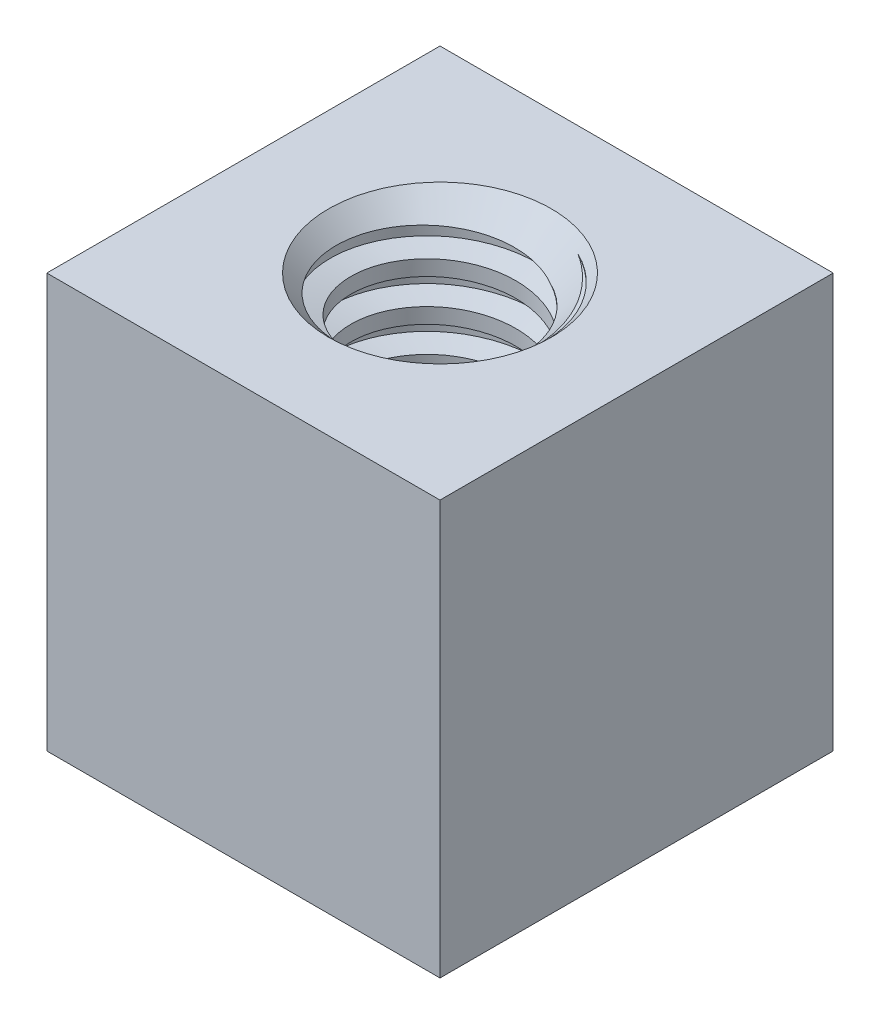
SolidWorks part; units mm, degrees
ref_plane "Front" through (0, 0, 0) normal (0, 0, 1) x (1, 0, 0)
ref_plane "Top" through (0, 0, 0) normal (0, 1, 0) x (1, 0, 0)
ref_plane "Right" through (0, 0, 0) normal (1, 0, 0) x (0, 0, -1)
sketch "Sketch1" plane through (0, 0, 0) normal (0, 1, 0) x (1, 0, 0)
  line L1 (-9.5, 9.5) -> (9.5, 9.5)
  line L2 (-9.5, 9.5) -> (-9.5, -9.5)
  line L3 (-9.5, -9.5) -> (9.5, -9.5)
  line L4 (9.5, 9.5) -> (9.5, -9.5)
  line L5 (-9.5, 9.5) -> (9.5, -9.5) construction
  line L6 (-9.5, -9.5) -> (9.5, 9.5) construction
  circle A0 centre (0, 0) radius 5
  dimension "Width" = 19
  dimension "ThreadDia" = 10
extrude "Boss-Extrude1" add sketch "Sketch1" along normal mid plane 20
sketch "Sketch2" plane through (0, 10, 0) normal (0, 1, 0) x (1, 0, 0)
  circle A0 centre (0, 0) radius 5 construction
  circle A1 centre (0, 0) radius 5
curve "Helix/Spiral1" pitch 2 height 22 radius 5 centre (0, 10, 0) axis (0, -1, 0) start towards (1, 0, 0) parameters "Pitch"=2
sketch "Sketch3" plane through (0, 0, 0) normal (0, 0, 1) x (1, 0, 0)
  line L0 (5, 10) -> (4.0001, 10.2586)
  line L1 (-9.5, 10) -> (9.5, 10) construction
  line L2 (4.0001, 10.2586) -> (4.0001, 11)
  line L3 (4.0001, 11) -> (5, 11.2586)
  line L4 (5, 11.2586) -> (5, 10)
  line L5 (4.5, 10.1293) -> (4.5, 11.1293) construction
  line L6 (4.5, 10.6293) -> (4.0001, 10.6293) construction
  spline S0 degree 3 poles (5, 10) (5, 9.9586) (4.7397, 9.8749) (3.6276, 9.75) (1.9632, 9.625) (0, 9.5) (-1.9632, 9.375) (-3.6276, 9.25) (-4.7397, 9.125) (-5.1302, 9) (-4.7397, 8.875) (-3.6276, 8.75) (-1.9632, 8.625) (0, 8.5) (1.9632, 8.375) (3.6276, 8.25) (4.7397, 8.125) (5.1302, 8) (4.7397, 7.875) (3.6276, 7.75) (1.9632, 7.625) (0, 7.5) (-1.9632, 7.375) (-3.6276, 7.25) (-4.7397, 7.125) (-5.1302, 7) (-4.7397, 6.875) (-3.6276, 6.75) (-1.9632, 6.625) (0, 6.5) (1.9632, 6.375) (3.6276, 6.25) (4.7397, 6.125) (5.1302, 6) (4.7397, 5.875) (3.6276, 5.75) (1.9632, 5.625) (0, 5.5) (-1.9632, 5.375) (-3.6276, 5.25) (-4.7397, 5.125) (-5.1302, 5) (-4.7397, 4.875) (-3.6276, 4.75) (-1.9632, 4.625) (0, 4.5) (1.9632, 4.375) (3.6276, 4.25) (4.7397, 4.125) (5.1302, 4) (4.7397, 3.875) (3.6276, 3.75) (1.9632, 3.625) (0, 3.5) (-1.9632, 3.375) (-3.6276, 3.25) (-4.7397, 3.125) (-5.1302, 3) (-4.7397, 2.875) (-3.6276, 2.75) (-1.9632, 2.625) (0, 2.5) (1.9632, 2.375) (3.6276, 2.25) (4.7397, 2.125) (5.1302, 2) (4.7397, 1.875) (3.6276, 1.75) (1.9632, 1.625) (0, 1.5) (-1.9632, 1.375) (-3.6276, 1.25) (-4.7397, 1.125) (-5.1302, 1) (-4.7397, 0.875) (-3.6276, 0.75) (-1.9632, 0.625) (0, 0.5) (1.9632, 0.375) (3.6276, 0.25) (4.7397, 0.125) (5.1302, 0) (4.7397, -0.125) (3.6276, -0.25) (1.9632, -0.375) (0, -0.5) (-1.9632, -0.625) (-3.6276, -0.75) (-4.7397, -0.875) (-5.1302, -1) (-4.7397, -1.125) (-3.6276, -1.25) (-1.9632, -1.375) (0, -1.5) (1.9632, -1.625) (3.6276, -1.75) (4.7397, -1.875) (5.1302, -2) (4.7397, -2.125) (3.6276, -2.25) (1.9632, -2.375) (0, -2.5) (-1.9632, -2.625) (-3.6276, -2.75) (-4.7397, -2.875) (-5.1302, -3) (-4.7397, -3.125) (-3.6276, -3.25) (-1.9632, -3.375) (0, -3.5) (1.9632, -3.625) (3.6276, -3.75) (4.7397, -3.875) (5.1302, -4) (4.7397, -4.125) (3.6276, -4.25) (1.9632, -4.375) (0, -4.5) (-1.9632, -4.625) (-3.6276, -4.75) (-4.7397, -4.875) (-5.1302, -5) (-4.7397, -5.125) (-3.6276, -5.25) (-1.9632, -5.375) (0, -5.5) (1.9632, -5.625) (3.6276, -5.75) (4.7397, -5.875) (5.1302, -6) (4.7397, -6.125) (3.6276, -6.25) (1.9632, -6.375) (0, -6.5) (-1.9632, -6.625) (-3.6276, -6.75) (-4.7397, -6.875) (-5.1302, -7) (-4.7397, -7.125) (-3.6276, -7.25) (-1.9632, -7.375) (0, -7.5) (1.9632, -7.625) (3.6276, -7.75) (4.7397, -7.875) (5.1302, -8) (4.7397, -8.125) (3.6276, -8.25) (1.9632, -8.375) (0, -8.5) (-1.9632, -8.625) (-3.6276, -8.75) (-4.7397, -8.875) (-5.1302, -9) (-4.7397, -9.125) (-3.6276, -9.25) (-1.9632, -9.375) (0, -9.5) (1.9632, -9.625) (3.6276, -9.75) (4.7397, -9.875) (5.1302, -10) (4.7397, -10.125) (3.6276, -10.25) (1.9632, -10.375) (0, -10.5) (-1.9632, -10.625) (-3.6276, -10.75) (-4.7397, -10.875) (-5.1302, -11) (-4.7397, -11.125) (-3.6276, -11.25) (-1.9632, -11.375) (0, -11.5) (1.9632, -11.625) (3.6276, -11.75) (4.7397, -11.8749) (5, -11.9586) (5, -12) knots 0 0 0 0 0.005682 0.011364 0.017045 0.022727 0.028409 0.034091 0.039773 0.045455 0.051136 0.056818 0.0625 0.068182 0.073864 0.079545 0.085227 0.090909 0.096591 0.102273 0.107955 0.113636 0.119318 0.125 0.130682 0.136364 0.142045 0.147727 0.153409 0.159091 0.164773 0.170455 0.176136 0.181818 0.1875 0.193182 0.198864 0.204545 0.210227 0.215909 0.221591 0.227273 0.232955 0.238636 0.244318 0.25 0.255682 0.261364 0.267045 0.272727 0.278409 0.284091 0.289773 0.295455 0.301136 0.306818 0.3125 0.318182 0.323864 0.329545 0.335227 0.340909 0.346591 0.352273 0.357955 0.363636 0.369318 0.375 0.380682 0.386364 0.392045 0.397727 0.403409 0.409091 0.414773 0.420455 0.426136 0.431818 0.4375 0.443182 0.448864 0.454545 0.460227 0.465909 0.471591 0.477273 0.482955 0.488636 0.494318 0.5 0.505682 0.511364 0.517045 0.522727 0.528409 0.534091 0.539773 0.545455 0.551136 0.556818 0.5625 0.568182 0.573864 0.579545 0.585227 0.590909 0.596591 0.602273 0.607955 0.613636 0.619318 0.625 0.630682 0.636364 0.642045 0.647727 0.653409 0.659091 0.664773 0.670455 0.676136 0.681818 0.6875 0.693182 0.698864 0.704545 0.710227 0.715909 0.721591 0.727273 0.732955 0.738636 0.744318 0.75 0.755682 0.761364 0.767045 0.772727 0.778409 0.784091 0.789773 0.795455 0.801136 0.806818 0.8125 0.818182 0.823864 0.829545 0.835227 0.840909 0.846591 0.852273 0.857955 0.863636 0.869318 0.875 0.880682 0.886364 0.892045 0.897727 0.903409 0.909091 0.914773 0.920455 0.926136 0.931818 0.9375 0.943182 0.948864 0.954545 0.960227 0.965909 0.971591 0.977273 0.982955 0.988636 0.994318 1 1 1 1 construction
  dimension "D1" = 29
  dimension "D2" = 0.7414
sketch "Sketch4" plane through (0, 10, 0) normal (0, 1, 0) x (1, 0, 0)
  circle A0 centre (0, 0) radius 5.381
  circle A1 centre (0, 0) radius 5 construction
  dimension "D1" = 0.381
sketch "Sketch5" plane through (0, -10, 0) normal (0, -1, 0) x (1, 0, 0)
  circle A1 centre (0, 0) radius 5.381
  circle A2 centre (0, 0) radius 5.381
  dimension "D1" = 0
sweep "Sweep1" add profiles "Sketch3" path "Helix/Spiral1"
extrude "Cut-Extrude1" cut sketch "Sketch4" along normal through all
extrude "Cut-Extrude2" cut sketch "Sketch5" along normal through all
extrude "Cut-Extrude3" cut sketch "Sketch4<2>" against normal through all draft 45
sketch "Sketch4<2>" plane through (0, 10, 0) normal (0, 1, 0) x (1, 0, 0) same geometry as "Sketch4"
extrude "Cut-Extrude4" cut sketch "Sketch5<2>" against normal through all draft 45
sketch "Sketch5<2>" plane through (0, -10, 0) normal (0, -1, 0) x (1, 0, 0) same geometry as "Sketch5"
equation "\"D3@Helix/Spiral1\" = \"Height@Boss-Extrude1\"+\"Pitch@Helix/Spiral1\""
equation "\"D2@Sketch3\" = \"Pitch@Helix/Spiral1\"*.3707"
equation "\"D3@Sketch3\" = \"Pitch@Helix/Spiral1\"*.5"
